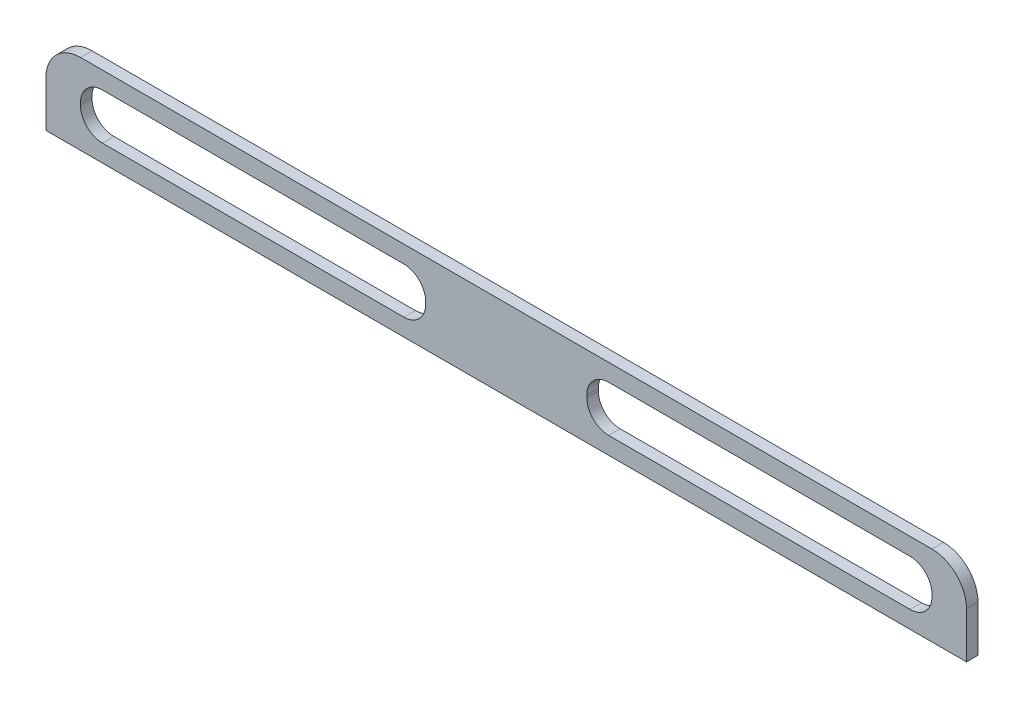
SolidWorks part; units mm, degrees
material "0.6010 (EN-GJL-100)"
ref_plane "Ön Düzlem" through (0, 0, 0) normal (0, 0, 1) x (1, 0, 0)
ref_plane "Üst Düzlem" through (0, 0, 0) normal (0, 1, 0) x (1, 0, 0)
ref_plane "Sağ Düzlem" through (0, 0, 0) normal (1, 0, 0) x (0, 0, -1)
sketch "Çizim1" plane through (0, 0, 0) normal (0, 0, 1) x (1, 0, 0)
  line L0 (351, 20) -> (89, 20)
  line L1 (400, -35) -> (-400, -35)
  line L2 (400, -35) -> (400, 5)
  line L3 (370, 35) -> (-370, 35)
  line L4 (-400, -35) -> (-400, 5)
  line L5 (-70, 1) -> (-70, -1)
  line L6 (-370, 1) -> (-370, -1)
  line L8 (351, -20) -> (89, -20)
  line L10 (-385, -20) -> (-385, 20) construction
  line L11 (385, -20) -> (-385, -20) construction
  line L12 (385, 20) -> (-385, 20) construction
  line L13 (385, -20) -> (385, 20) construction
  line L16 (-89, 20) -> (-351, 20)
  line L17 (370, 1) -> (370, -1)
  line L18 (70, 1) -> (70, -1)
  line L19 (-89, -20) -> (-351, -20)
  line L20 (400, -35) -> (400, 35) construction
  line L21 (400, 35) -> (-400, 35) construction
  line L22 (-400, -35) -> (-400, 35) construction
  arc A8 (400, 5) -> (370, 35) centre (370, 5) ccw
  arc A9 (-370, 35) -> (-400, 5) centre (-370, 5) ccw
  arc A10 (-89, -20) -> (-70, -1) centre (-89, -1) ccw
  arc A11 (-89, 20) -> (-70, 1) centre (-89, 1) cw
  arc A12 (-351, -20) -> (-370, -1) centre (-351, -1) cw
  arc A13 (-351, 20) -> (-370, 1) centre (-351, 1) ccw
  arc A14 (89, -20) -> (70, -1) centre (89, -1) cw
  arc A15 (89, 20) -> (70, 1) centre (89, 1) ccw
  arc A16 (351, -20) -> (370, -1) centre (351, -1) ccw
  arc A17 (351, 20) -> (370, 1) centre (351, 1) cw
  point P0 (0, 0)
  point P14 (-70, -20)
  point P20 (-70, 20)
  point P24 (-370, -20)
  point P27 (-370, 20)
  point P30 (70, -20)
  point P35 (70, 20)
  point P37 (-85, -20)
  point P39 (370, -20)
  point P48 (370, 20)
  dimension "D4" = 300
  dimension "D5" = 15
  dimension "D8" = 30
  dimension "D9" = 300
  dimension "D1" = 30
  dimension "D10" = 19
  dimension "D2" = 30
  dimension "D6" = 300
  dimension "D7" = 30
  dimension "D3" = 300
base flange "Taban-Flanş1" sketch "Çizim1" thickness 10 reverse thickness direction no parameters "D1"=0.7366
sketch "Büküm-Çizgileri1" [suppressed] plane through (0, 0, 0) normal (0, 1, 0) x (1, 0, 0)
sketch "Sınırlandırma-Kutusu1" [suppressed] plane through (0, 0, 0) normal (0, 1, 0) x (1, 0, 0)
sheet metal parameters "Sac-Levha1" thickness 10 parameters "D1"=0.7366
flat pattern "Düz-Çoğaltma1" [suppressed]
sketch "Büküm-Çizgileri2" plane through (0, 0, 0) normal (0, 1, 0) x (1, 0, 0)
sketch3d "Sınırlandırma-Kutusu2" [suppressed]
  line L0 (-770, -40, 0) -> (30, -40, 0) construction
  line L1 (-770, 30, 0) -> (30, 30, 0) construction
  line L2 (-770, -40, 0) -> (-770, 30, 0) construction
  line L3 (30, -40, 0) -> (30, 30, 0) construction
